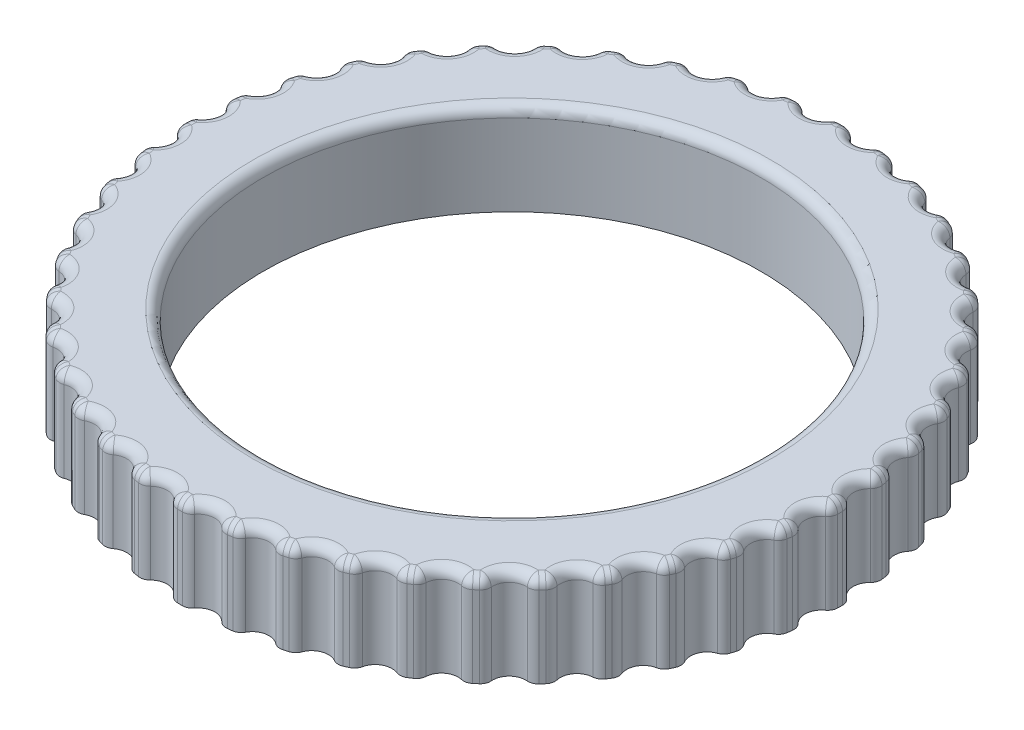
SolidWorks part; units mm, degrees
ref_plane "Plan de face" through (0, 0, 0) normal (0, 0, 1) x (1, 0, 0)
ref_plane "Plan de dessus" through (0, 0, 0) normal (0, 1, 0) x (1, 0, 0)
ref_plane "Plan de droite" through (0, 0, 0) normal (1, 0, 0) x (0, 0, -1)
sketch "Esquisse1" plane through (0, 0, 0) normal (0, 1, 0) x (1, 0, 0)
  circle A0 centre (0, 0) radius 4.9
  circle A1 centre (0, 0) radius 6.5
  dimension "D1" = 9.8
  dimension "D2" = 13
extrude "Boss.-Extru.1" add sketch "Esquisse1" along normal blind 1.8
sketch "Esquisse2" plane through (0, 1.8, 0) normal (0, 1, 0) x (1, 0, 0)
  circle A0 centre (0, 0) radius 6.3 construction
  circle A1 centre (0, 0) radius 6.5 construction
  circle A2 centre (-0.4345, 6.6154) radius 0.3296
  circle A3 centre (0.5114, 6.6099) radius 0.3296
  circle A4 centre (1.4469, 6.4698) radius 0.3296
  circle A5 centre (2.3529, 6.198) radius 0.3296
  circle A6 centre (3.211, 5.8001) radius 0.3296
  circle A7 centre (4.0038, 5.2841) radius 0.3296
  circle A8 centre (4.715, 4.6605) radius 0.3296
  circle A9 centre (5.3303, 3.9421) radius 0.3296
  circle A10 centre (5.837, 3.1434) radius 0.3296
  circle A11 centre (6.225, 2.2807) radius 0.3296
  circle A12 centre (6.4862, 1.3715) radius 0.3296
  circle A13 centre (6.6154, 0.4345) radius 0.3296
  circle A14 centre (6.6099, -0.5114) radius 0.3296
  circle A15 centre (6.4698, -1.4469) radius 0.3296
  circle A16 centre (6.198, -2.3529) radius 0.3296
  circle A17 centre (5.8001, -3.211) radius 0.3296
  circle A18 centre (5.2841, -4.0038) radius 0.3296
  circle A19 centre (4.6605, -4.715) radius 0.3296
  circle A20 centre (3.9421, -5.3303) radius 0.3296
  circle A21 centre (3.1434, -5.837) radius 0.3296
  circle A22 centre (2.2807, -6.225) radius 0.3296
  circle A23 centre (1.3715, -6.4862) radius 0.3296
  circle A24 centre (0.4345, -6.6154) radius 0.3296
  circle A25 centre (-0.5114, -6.6099) radius 0.3296
  circle A26 centre (-1.4469, -6.4698) radius 0.3296
  circle A27 centre (-2.3529, -6.198) radius 0.3296
  circle A28 centre (-3.211, -5.8001) radius 0.3296
  circle A29 centre (-4.0038, -5.2841) radius 0.3296
  circle A30 centre (-4.715, -4.6605) radius 0.3296
  circle A31 centre (-5.3303, -3.9421) radius 0.3296
  circle A32 centre (-5.837, -3.1434) radius 0.3296
  circle A33 centre (-6.225, -2.2807) radius 0.3296
  circle A34 centre (-6.4862, -1.3715) radius 0.3296
  circle A35 centre (-6.6154, -0.4345) radius 0.3296
  circle A36 centre (-6.6099, 0.5114) radius 0.3296
  circle A37 centre (-6.4698, 1.4469) radius 0.3296
  circle A38 centre (-6.198, 2.3529) radius 0.3296
  circle A39 centre (-5.8001, 3.211) radius 0.3296
  circle A40 centre (-5.2841, 4.0038) radius 0.3296
  circle A41 centre (-4.6605, 4.715) radius 0.3296
  circle A42 centre (-3.9421, 5.3303) radius 0.3296
  circle A43 centre (-3.1434, 5.837) radius 0.3296
  circle A44 centre (-2.2807, 6.225) radius 0.3296
  circle A45 centre (-1.3715, 6.4862) radius 0.3296
  point P9 (-0.7249, 6.4595)
  point P10 (-0.1262, 6.4988)
  point P98 (0, 0)
  dimension "D1" = 0.2
  dimension "D2" = 0.5987
  dimension "D3" = 44
extrude "Enlèv. mat.-Extru.1" cut sketch "Esquisse2" against normal blind 1.8
fillet "Congé2" radius 0.2 88 edges at (-5.8968, 1.8, -2.7345) (-0.8876, 1.8, -6.4391) (-0.4129, 1.8, -6.2865) (0.0378, 1.8, -6.4999) (0.486, 1.8, -6.2812) (0.9624, 1.8, -6.4284) (1.3749, 1.8, -6.1481) (1.8675, 1.8, -6.226) (2.2359, 1.8, -5.8899) (2.7345, 1.8, -5.8968) (3.0514, 1.8, -5.5117) (3.5459, 1.8, -5.4476) (3.8047, 1.8, -5.0214) (4.2851, 1.8, -4.8875) (4.4806, 1.8, -4.4288) (4.937, 1.8, -4.228) (5.0653, 1.8, -3.7461) (5.4885, 1.8, -3.4823) (5.5468, 1.8, -2.9871) (5.9282, 1.8, -2.6658) (5.9155, 1.8, -2.1673) (6.2472, 1.8, -1.795) (6.1637, 1.8, -1.3034) (6.4391, 1.8, -0.8876) (6.2865, 1.8, -0.4129) (6.4999, 1.8, 0.0378) (6.2812, 1.8, 0.486) (6.4284, 1.8, 0.9624) (6.1481, 1.8, 1.3749) (6.226, 1.8, 1.8675) (5.8899, 1.8, 2.2359) (5.8968, 1.8, 2.7345) (5.5117, 1.8, 3.0514) (5.4476, 1.8, 3.5459) (5.0214, 1.8, 3.8047) (4.8875, 1.8, 4.2851) (4.4288, 1.8, 4.4806) (4.228, 1.8, 4.937) (3.7461, 1.8, 5.0653) (3.4823, 1.8, 5.4885) (2.9871, 1.8, 5.5468) (2.6658, 1.8, 5.9282) (2.1673, 1.8, 5.9155) (1.795, 1.8, 6.2472) (1.3034, 1.8, 6.1637) (0.8876, 1.8, 6.4391) (0.4129, 1.8, 6.2865) (-0.0378, 1.8, 6.4999) (-0.486, 1.8, 6.2812) (-0.9624, 1.8, 6.4284) (-1.3749, 1.8, 6.1481) (-1.8675, 1.8, 6.226) (-2.2359, 1.8, 5.8899) (-2.7345, 1.8, 5.8968) (-3.0514, 1.8, 5.5117) (-3.5459, 1.8, 5.4476) (-3.8047, 1.8, 5.0214) (-4.2851, 1.8, 4.8875) (-4.4806, 1.8, 4.4288) (-4.937, 1.8, 4.228) (-5.0653, 1.8, 3.7461) (-5.4885, 1.8, 3.4823) (-5.5468, 1.8, 2.9871) (-5.9282, 1.8, 2.6658) (-5.9155, 1.8, 2.1673) (-6.2472, 1.8, 1.795) (-6.1637, 1.8, 1.3034) (-6.4391, 1.8, 0.8876) (-6.2865, 1.8, 0.4129) (-6.4999, 1.8, -0.0378) (-6.2812, 1.8, -0.486) (-6.4284, 1.8, -0.9624) (-6.1481, 1.8, -1.3749) (-6.226, 1.8, -1.8675) (-5.8899, 1.8, -2.2359) (-5.5117, 1.8, -3.0514) (-5.0214, 1.8, -3.8047) (-4.8875, 1.8, -4.2851) (-4.4288, 1.8, -4.4806) (-4.228, 1.8, -4.937) (-3.7461, 1.8, -5.0653) (-3.4823, 1.8, -5.4885) (-2.9871, 1.8, -5.5468) (-2.6658, 1.8, -5.9282) (-2.1673, 1.8, -5.9155) (-1.795, 1.8, -6.2472) (-1.3034, 1.8, -6.1637) (-5.4476, 1.8, -3.5459)
fillet "Congé3" radius 0.2 1 edges at (0, 1.8, 4.9)
fillet "Congé4" radius 0.2 176 edges at (-1.9214, 1.7102, -6.1749) (-2.5225, 1.7102, -5.9547) (-2.7807, 1.7102, -5.8386) (-3.3443, 1.7102, -5.5351) (-3.5833, 1.7102, -5.3834) (-4.0979, 1.7102, -5.0028) (-4.9548, 1.7102, -4.1558) (-5.3414, 1.7102, -3.6456) (-5.4958, 1.7102, -3.4084) (-5.8058, 1.7102, -2.8484) (-5.9249, 1.7102, -2.5915) (-6.1521, 1.7102, -1.9931) (-6.2334, 1.7102, -1.722) (-6.3731, 1.7102, -1.0973) (-6.4151, 1.7102, -0.8173) (-6.4644, 1.7102, -0.1791) (-6.4661, 1.7102, 0.104) (-6.4241, 1.7102, 0.7427) (-6.3855, 1.7102, 1.0231) (-6.253, 1.7102, 1.6494) (-6.1749, 1.7102, 1.9214) (-5.9547, 1.7102, 2.5225) (-5.8386, 1.7102, 2.7807) (-5.5351, 1.7102, 3.3443) (-5.3834, 1.7102, 3.5833) (-5.0028, 1.7102, 4.0979) (-4.8187, 1.7102, 4.3129) (-4.3687, 1.7102, 4.7682) (-4.1558, 1.7102, 4.9548) (-3.6456, 1.7102, 5.3414) (-3.4084, 1.7102, 5.4958) (-2.8484, 1.7102, 5.8058) (-2.5915, 1.7102, 5.9249) (-1.9931, 1.7102, 6.1521) (-1.722, 1.7102, 6.2334) (-1.0973, 1.7102, 6.3731) (-0.8173, 1.7102, 6.4151) (-0.1791, 1.7102, 6.4644) (0.104, 1.7102, 6.4661) (0.7427, 1.7102, 6.4241) (1.0231, 1.7102, 6.3855) (1.6494, 1.7102, 6.253) (1.9214, 1.7102, 6.1749) (2.5225, 1.7102, 5.9547) (2.7807, 1.7102, 5.8386) (3.3443, 1.7102, 5.5351) (3.5833, 1.7102, 5.3834) (4.0979, 1.7102, 5.0028) (4.3129, 1.7102, 4.8187) (4.7682, 1.7102, 4.3687) (4.9548, 1.7102, 4.1558) (5.3414, 1.7102, 3.6456) (5.4958, 1.7102, 3.4084) (5.8058, 1.7102, 2.8484) (5.9249, 1.7102, 2.5915) (6.1521, 1.7102, 1.9931) (6.2334, 1.7102, 1.722) (6.3731, 1.7102, 1.0973) (6.4151, 1.7102, 0.8173) (6.4644, 1.7102, 0.1791) (6.4661, 1.7102, -0.104) (6.4241, 1.7102, -0.7427) (6.3855, 1.7102, -1.0231) (6.253, 1.7102, -1.6494) (6.1749, 1.7102, -1.9214) (5.9547, 1.7102, -2.5225) (5.8386, 1.7102, -2.7807) (5.5351, 1.7102, -3.3443) (5.3834, 1.7102, -3.5833) (5.0028, 1.7102, -4.0979) (4.8187, 1.7102, -4.3129) (4.3687, 1.7102, -4.7682) (4.1558, 1.7102, -4.9548) (3.6456, 1.7102, -5.3414) (3.4084, 1.7102, -5.4958) (2.8484, 1.7102, -5.8058) (2.5915, 1.7102, -5.9249) (1.9931, 1.7102, -6.1521) (1.722, 1.7102, -6.2334) (1.0973, 1.7102, -6.3731) (0.8173, 1.7102, -6.4151) (0.1791, 1.7102, -6.4644) (-0.104, 1.7102, -6.4661) (-0.7427, 1.7102, -6.4241) (-1.0231, 1.7102, -6.3855) (-1.6494, 1.7102, -6.253) (-4.3129, 1.7102, -4.8187) (-4.7682, 1.7102, -4.3687) (-1.952, 0.8, -6.2) (-2.5154, 0.8, -5.9936) (-2.8145, 0.8, -5.8591) (-3.3428, 0.8, -5.5746) (-3.6197, 0.8, -5.3989) (-4.1021, 0.8, -5.0421) (-4.9941, 0.8, -4.1604) (-5.3564, 0.8, -3.6822) (-5.5353, 0.8, -3.4073) (-5.826, 0.8, -2.8824) (-5.9639, 0.8, -2.5849) (-6.1769, 0.8, -2.024) (-6.2711, 0.8, -1.7098) (-6.402, 0.8, -1.1243) (-6.4506, 0.8, -0.8) (-6.4969, 0.8, -0.2017) (-6.4988, 0.8, 0.1262) (-6.4595, 0.8, 0.7249) (-6.4147, 0.8, 1.0498) (-6.2905, 0.8, 1.6368) (-6.2, 0.8, 1.952) (-5.9936, 0.8, 2.5154) (-5.8591, 0.8, 2.8145) (-5.5746, 0.8, 3.3428) (-5.3989, 0.8, 3.6197) (-5.0421, 0.8, 4.1021) (-4.8288, 0.8, 4.3512) (-4.407, 0.8, 4.7779) (-4.1604, 0.8, 4.9941) (-3.6822, 0.8, 5.3564) (-3.4073, 0.8, 5.5353) (-2.8824, 0.8, 5.826) (-2.5849, 0.8, 5.9639) (-2.024, 0.8, 6.1769) (-1.7098, 0.8, 6.2711) (-1.1243, 0.8, 6.402) (-0.8, 0.8, 6.4506) (-0.2017, 0.8, 6.4969) (0.1262, 0.8, 6.4988) (0.7249, 0.8, 6.4595) (1.0498, 0.8, 6.4147) (1.6368, 0.8, 6.2905) (1.952, 0.8, 6.2) (2.5154, 0.8, 5.9936) (2.8145, 0.8, 5.8591) (3.3428, 0.8, 5.5746) (3.6197, 0.8, 5.3989) (4.1021, 0.8, 5.0421) (4.3512, 0.8, 4.8288) (4.7779, 0.8, 4.407) (4.9941, 0.8, 4.1604) (5.3564, 0.8, 3.6822) (5.5353, 0.8, 3.4073) (5.826, 0.8, 2.8824) (5.9639, 0.8, 2.5849) (6.1769, 0.8, 2.024) (6.2711, 0.8, 1.7098) (6.402, 0.8, 1.1243) (6.4506, 0.8, 0.8) (6.4969, 0.8, 0.2017) (6.4988, 0.8, -0.1262) (6.4595, 0.8, -0.7249) (6.4147, 0.8, -1.0498) (6.2905, 0.8, -1.6368) (6.2, 0.8, -1.952) (5.9936, 0.8, -2.5154) (5.8591, 0.8, -2.8145) (5.5746, 0.8, -3.3428) (5.3989, 0.8, -3.6197) (5.0421, 0.8, -4.1021) (4.8288, 0.8, -4.3512) (4.407, 0.8, -4.7779) (4.1604, 0.8, -4.9941) (3.6822, 0.8, -5.3564) (3.4073, 0.8, -5.5353) (2.8824, 0.8, -5.826) (2.5849, 0.8, -5.9639) (2.024, 0.8, -6.1769) (1.7098, 0.8, -6.2711) (1.1243, 0.8, -6.402) (0.8, 0.8, -6.4506) (0.2017, 0.8, -6.4969) (-0.1262, 0.8, -6.4988) (-0.7249, 0.8, -6.4595) (-1.0498, 0.8, -6.4147) (-1.6368, 0.8, -6.2905) (-4.3512, 0.8, -4.8288) (-4.7779, 0.8, -4.407)
